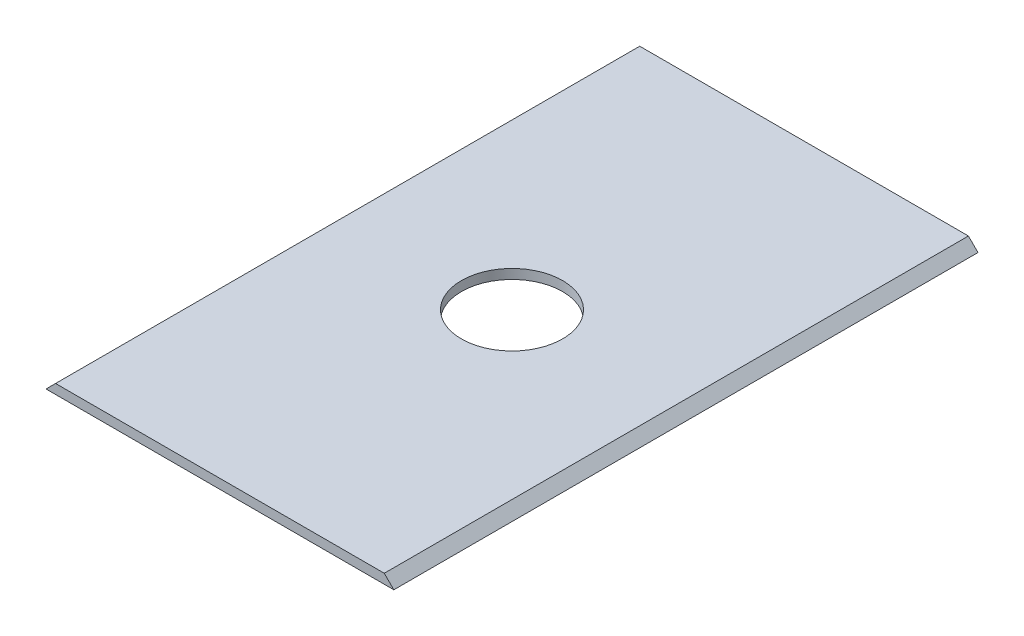
SolidWorks part; units mm, degrees
ref_plane "Front Plane" through (0, 0, 0) normal (0, 0, 1) x (1, 0, 0)
ref_plane "Top Plane" through (0, 0, 0) normal (0, 1, 0) x (1, 0, 0)
ref_plane "Right Plane" through (0, 0, 0) normal (1, 0, 0) x (0, 0, -1)
sketch "Sketch1" plane through (0, 0, 0) normal (0, 0, 1) x (1, 0, 0)
  line L0 (0, 0) -> (65.5, 0)
  line L1 (65.5, 0) -> (63.7, 1.8)
  line L2 (63.7, 1.8) -> (1.8, 1.8)
  line L3 (1.8, 1.8) -> (0, 0)
  dimension "D1" = 1.8
  dimension "D2" = 65.5
  dimension "D3" = 45
extrude "Boss-Extrude1" add sketch "Sketch1" along normal blind 110
sketch "Sketch2" plane through (0, 1.8, 0) normal (0, 1, 0) x (1, 0, 0)
  line L0 (32.75, -110) -> (32.75, 0) construction
  line L1 (63.7, -110) -> (1.8, -110) construction
  line L2 (63.7, 0) -> (1.8, 0) construction
  line L3 (1.8, -55) -> (63.7, -55) construction
  line L4 (1.8, -110) -> (1.8, 0) construction
  line L5 (63.7, -110) -> (63.7, 0) construction
  circle A0 centre (32.75, -55) radius 9.525
  point P14 (0, 0)
  dimension "D1" = 19.05
extrude "Cut-Extrude1" cut sketch "Sketch2" against normal through all
